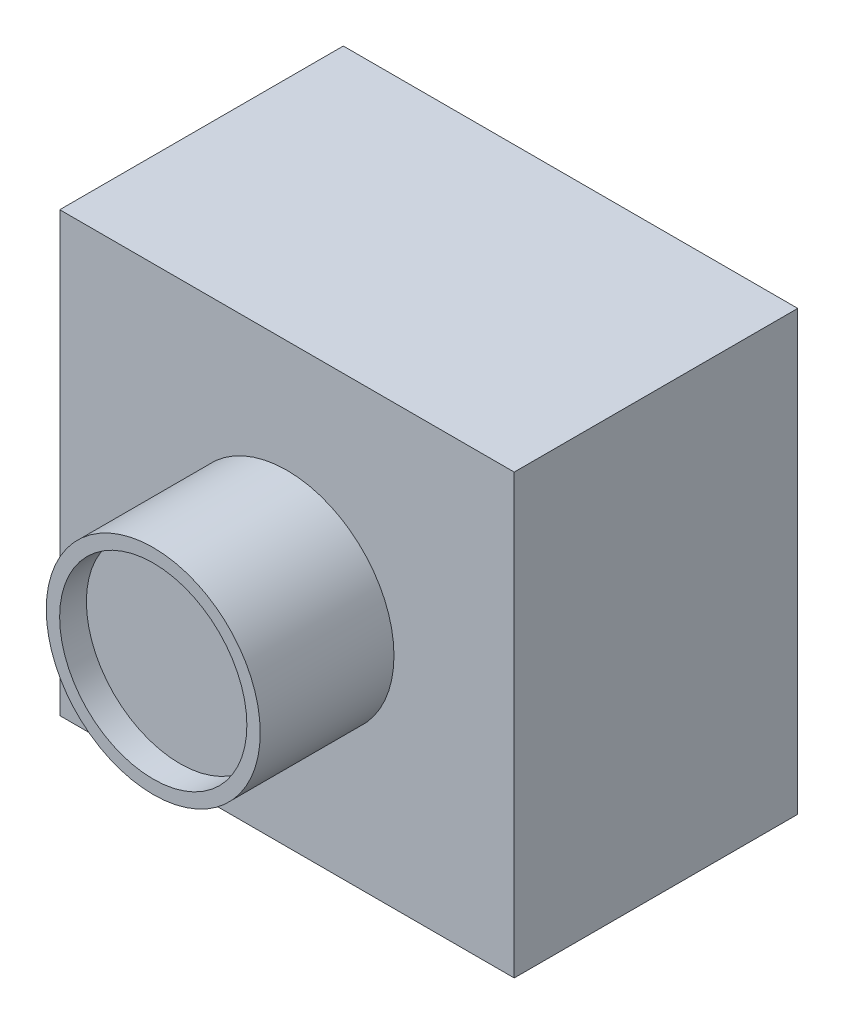
SolidWorks part; units mm, degrees
material "EHS"
ref_plane "Piano frontale" through (0, 0, 0) normal (0, 0, 1) x (1, 0, 0)
ref_plane "Piano superiore" through (0, 0, 0) normal (0, 1, 0) x (1, 0, 0)
ref_plane "Piano destro" through (0, 0, 0) normal (1, 0, 0) x (0, 0, -1)
sketch "Schizzo1" plane through (0, 0, 0) normal (0, 0, 1) x (1, 0, 0)
  line L1 (-84.95, -81.9) -> (84.95, -81.9)
  line L2 (-84.95, -81.9) -> (-84.95, 81.9)
  line L3 (-84.95, 81.9) -> (84.95, 81.9)
  line L4 (84.95, -81.9) -> (84.95, 81.9)
  line L5 (-84.95, -81.9) -> (84.95, 81.9) construction
  line L6 (-84.95, 81.9) -> (84.95, -81.9) construction
  point P0 (0, 0)
  dimension "D1" = 169.9
  dimension "D2" = 163.8
extrude "Estrusione-Estrusione1" add sketch "Schizzo1" along normal blind 78 and the other way blind 78
sketch "Schizzo2" plane through (0, 0, 78) normal (0, 0, 1) x (1, 0, 0)
  line L0 (-84.95, 81.9) -> (-84.95, -81.9)
  line L1 (-84.95, -81.9) -> (84.95, -81.9)
  line L2 (84.95, -81.9) -> (84.95, 81.9)
  line L3 (84.95, 81.9) -> (-84.95, 81.9)
  circle A0 centre (0, 0) radius 40
  dimension "D1" = 80
extrude "Taglio-Estrusione1" cut sketch "Schizzo2" against normal blind 50
sketch "Schizzo3" plane through (0, 0, 78) normal (0, 0, 1) x (1, 0, 0)
  circle A0 centre (0, 0) radius 35
  dimension "D1" = 70
extrude "Taglio-Estrusione2" cut sketch "Schizzo3" against normal blind 10
